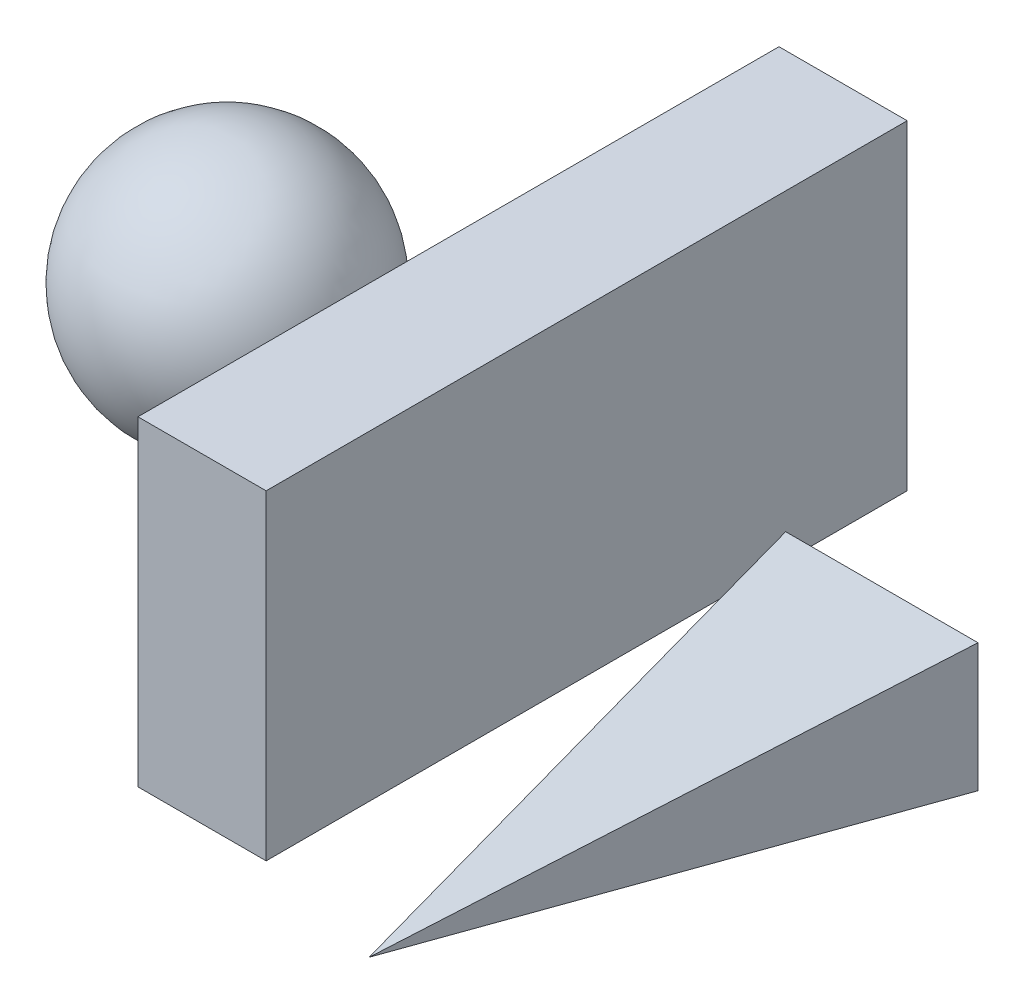
SolidWorks part; units mm, degrees
ref_plane "Front Plane" through (0, 0, 0) normal (0, 0, 1) x (1, 0, 0)
ref_plane "Top Plane" through (0, 0, 0) normal (0, 1, 0) x (1, 0, 0)
ref_plane "Right Plane" through (0, 0, 0) normal (1, 0, 0) x (0, 0, -1)
sketch "Sketch1" plane through (0, 0, 0) normal (0, 0, 1) x (1, 0, 0)
  line L1 (-25.4, -63.5) -> (25.4, -63.5)
  line L2 (-25.4, -63.5) -> (-25.4, 63.5)
  line L3 (-25.4, 63.5) -> (25.4, 63.5)
  line L4 (25.4, -63.5) -> (25.4, 63.5)
  line L5 (-25.4, -63.5) -> (25.4, 63.5) construction
  line L6 (-25.4, 63.5) -> (25.4, -63.5) construction
  point P0 (0, 0)
  dimension "D1" = 50.8
  dimension "D2" = 127
extrude "RecPrism" add sketch "Sketch1" along normal mid plane 254
sketch "Sphere" plane through (0, 0, 0) normal (0, 0, 1) x (1, 0, 0)
  line L1 (-117.0701, 50.7782) -> (-117.0701, -0.0218)
  line L2 (-117.0701, -0.0218) -> (-117.0701, -50.8218)
  arc A0 (-117.0701, 50.7782) -> (-117.0701, -50.8218) centre (-117.0701, -0.0218) ccw
  dimension "D1" = 50.8
sketch "PyramidBase" plane through (0, 0, 0) normal (0, 0, 1) x (1, 0, 0)
  line L1 (104.2662, -25.4) -> (180.4662, -25.4)
  line L2 (104.2662, -25.4) -> (104.2662, 25.4)
  line L3 (104.2662, 25.4) -> (180.4662, 25.4)
  line L4 (180.4662, -25.4) -> (180.4662, 25.4)
  line L5 (104.2662, -25.4) -> (180.4662, 25.4) construction
  line L6 (104.2662, 25.4) -> (180.4662, -25.4) construction
  point P0 (142.3662, 0)
  dimension "D1" = 76.2
  dimension "D2" = 50.8
ref_plane "PyramidPlane" through (142.3662, 0, 0) normal (1, 0, 0) x (0, 0, -1)
sketch "PyramidHeight" plane through (142.3662, 0, 0) normal (1, 0, 0) x (0, 0, -1)
  line L0 (0, 0) -> (-203.2, 0)
  dimension "D1" = 203.2
extrude "Pyramid" add sketch "PyramidBase" along normal up to vertex (203.2 mm away) separate body up to point (142.3662, 0, 203.2)
sketch "Sketch5" plane through (0, 0, 0) normal (0, 1, 0) x (1, 0, 0)
  line L0 (180.4662, 0) -> (142.3662, -203.2)
  line L1 (180.4662, -203.2) -> (104.2662, -203.2) construction
  line L2 (142.3662, -203.2) -> (104.2662, 0)
  line L3 (104.2662, 0) -> (180.4662, 0)
extrude "Cut-Extrude1" cut sketch "Sketch5" against normal through all both and the other way through all flip side to cut
sketch "Sketch6" plane through (142.3662, 0, 0) normal (1, 0, 0) x (0, 0, -1)
  line L0 (-203.2, 0) -> (0, 25.4)
  line L1 (0, 25.4) -> (0, -25.4)
  line L2 (0, -25.4) -> (-203.2, 0)
extrude "Cut-Extrude2" cut sketch "Sketch6" against normal through all both and the other way through all flip side to cut
revolve "SphereRevolve" add sketch "Sphere" angle 360 about L1
equation "\"sphere_radius\" = 2"
equation "\"prism_length\" = 5"
equation "\"prism_width\" = 2"
equation "\"prism_height\" = 10"
equation "\"pyramid_length\" = 3"
equation "\"pyramid_width\" = 2"
equation "\"pyramid_height\" = 8"
equation "\"D1@Sketch1\"=\"prism_width\""
equation "\"D2@Sketch1\"=\"prism_length\""
equation "\"D1@RecPrism\"=\"prism_height\""
equation "\"D1@PyramidBase\"=\"pyramid_length\""
equation "\"D2@PyramidBase\"=\"pyramid_width\""
equation "\"D1@PyramidHeight\"=\"pyramid_height\""
equation "\"D1@Sphere\"=\"sphere_radius\""
